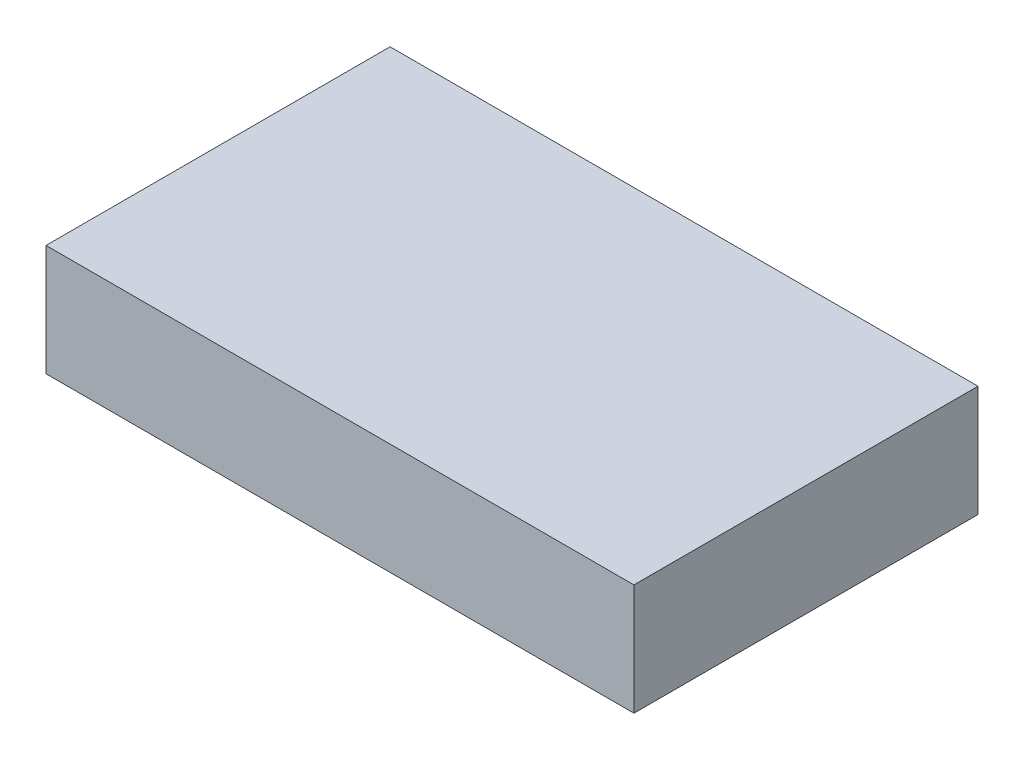
SolidWorks part; units mm, degrees
ref_plane "Front Plane" through (0, 0, 0) normal (0, 0, 1) x (1, 0, 0)
ref_plane "Top Plane" through (0, 0, 0) normal (0, 1, 0) x (1, 0, 0)
ref_plane "Right Plane" through (0, 0, 0) normal (1, 0, 0) x (0, 0, -1)
sketch "Sketch2" plane through (0, 0, 0) normal (0, 0, 1) x (1, 0, 0)
  line L0 (11.1072, -2.1) -> (-11.1072, -2.1)
  line L1 (-11.1072, -2.1) -> (-11.1072, 2.1)
  line L2 (-11.1072, 2.1) -> (11.1072, 2.1)
  line L3 (11.1072, 2.1) -> (11.1072, -2.1)
extrude "Boss-Extrude1" add sketch "Sketch2" along normal blind 13
